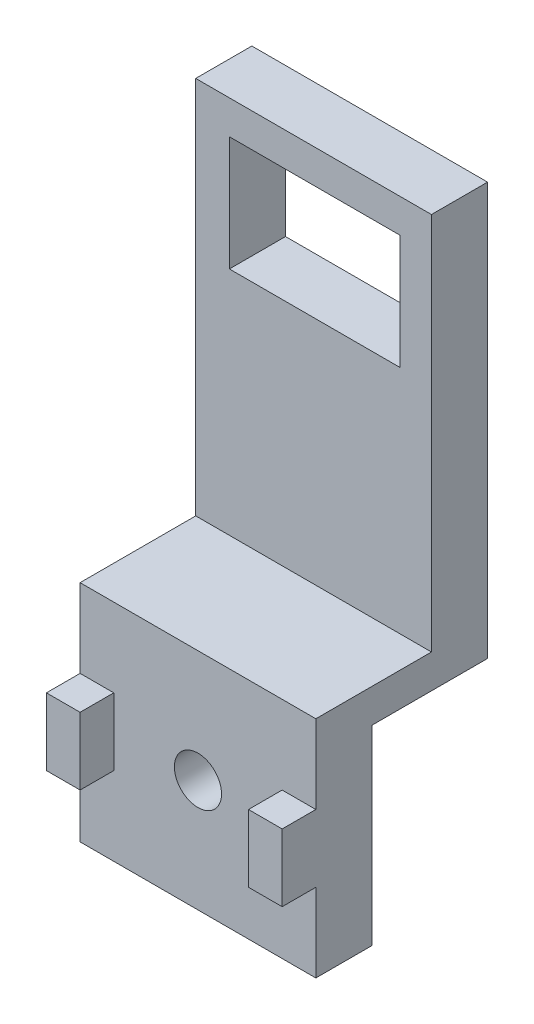
SolidWorks part; units mm, degrees
ref_plane "Front Plane" through (0, 0, 0) normal (0, 0, 1) x (1, 0, 0)
ref_plane "Top Plane" through (0, 0, 0) normal (0, 1, 0) x (1, 0, 0)
ref_plane "Right Plane" through (0, 0, 0) normal (1, 0, 0) x (0, 0, -1)
sketch "Sketch1" plane through (0, 0, 0) normal (0, 0, 1) x (1, 0, 0)
  line L1 (0, 0) -> (21, 0)
  line L2 (0, 0) -> (0, 53.75)
  line L3 (0, 53.75) -> (21, 53.75)
  line L4 (21, 0) -> (21, 53.75)
  line L5 (3, 50.75) -> (18.2, 50.75)
  line L6 (3, 50.75) -> (3, 40.55)
  line L7 (3, 40.55) -> (18.2, 40.55)
  line L8 (18.2, 50.75) -> (18.2, 40.55)
  circle A1 centre (10.5, 10) radius 2.1
  dimension "D6" = 4.2
  dimension "D9" = 10.5
  dimension "D1" = 10.2
  dimension "D2" = 15.2
  dimension "D3" = 21
  dimension "D4" = 3
  dimension "D5" = 3
  dimension "D7" = 10
  dimension "D11" = 40.55
extrude "Boss-Extrude1" add sketch "Sketch1" along normal blind 15.3
sketch "Sketch2" plane through (0, 0, 0) normal (-1, 0, 0) x (0, 0, 1)
  line L0 (15.3, 53.75) -> (0, 53.75) construction
  line L1 (15.3, 53.75) -> (5, 53.75)
  line L2 (15.3, 53.75) -> (15.3, 20)
  line L3 (15.3, 20) -> (5, 20)
  line L4 (5, 53.75) -> (5, 20)
  line L5 (15.3, 53.75) -> (15.3, 0) construction
  line L6 (0, 53.75) -> (0, 0) construction
  line L7 (0, 0) -> (10.3, 0)
  line L8 (0, 0) -> (0, 17)
  line L9 (0, 17) -> (10.3, 17)
  line L10 (10.3, 0) -> (10.3, 17)
  dimension "D1" = 17
  dimension "D2" = 3
  dimension "D3" = 5
  dimension "D4" = 5
extrude "Cut-Extrude1" cut sketch "Sketch2" against normal blind 21 contours L2 L1 L4 L3 | L8 L7 L10 L9
sketch "Sketch3" plane through (0, 0, 15.3) normal (0, 0, 1) x (1, 0, 0)
  line L0 (0, 20) -> (0, 0) construction
  line L1 (0, 13) -> (3, 13)
  line L2 (0, 13) -> (0, 7)
  line L3 (0, 7) -> (3, 7)
  line L4 (3, 13) -> (3, 7)
  line L5 (21, 0) -> (21, 20) construction
  line L6 (21, 13) -> (21, 7)
  line L7 (18, 13) -> (18, 7)
  line L8 (18, 13) -> (21, 13)
  line L9 (18, 7) -> (21, 7)
  point P8 (21, 10)
  point P9 (3, 10)
  dimension "D1" = 6
  dimension "D2" = 0
  dimension "D3" = 3
  dimension "D5" = 0
  dimension "D4" = 2
extrude "Boss-Extrude2" add sketch "Sketch3" along normal blind 3
